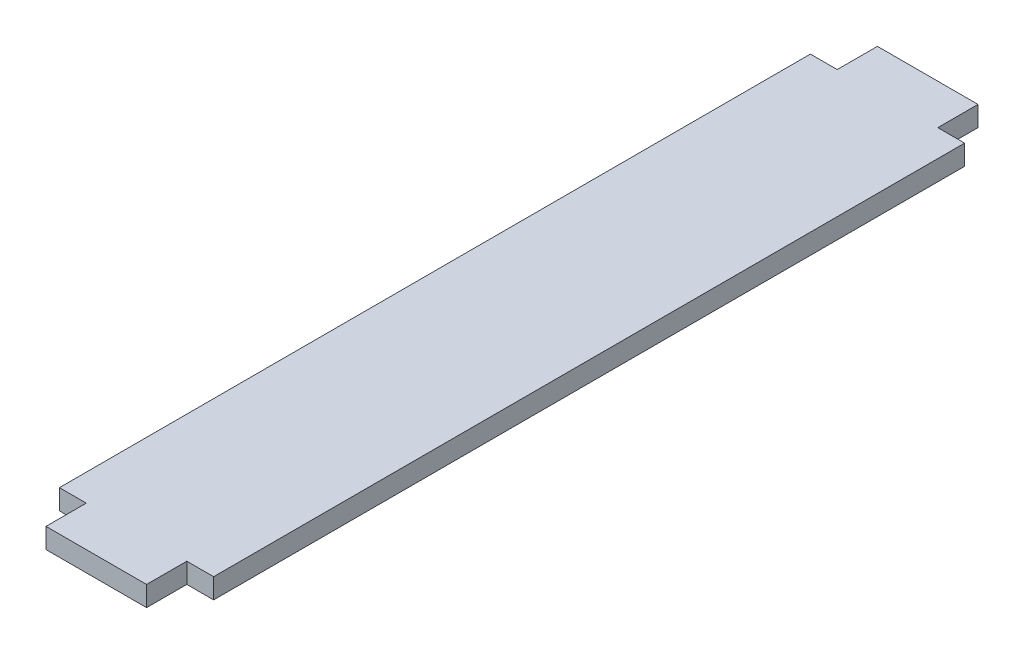
SolidWorks part; units mm, degrees
material "AISI 304"
ref_plane "Front Plane" through (0, 0, 0) normal (0, 0, 1) x (1, 0, 0)
ref_plane "Top Plane" through (0, 0, 0) normal (0, 1, 0) x (1, 0, 0)
ref_plane "Right Plane" through (0, 0, 0) normal (1, 0, 0) x (0, 0, -1)
sketch "Sketch1" plane through (0, 0, 0) normal (0, 1, 0) x (1, 0, 0)
  line L0 (3.75, 28) -> (5.75, 28)
  line L1 (-5.75, -28) -> (-3.75, -28)
  line L2 (-5.75, -28) -> (-5.75, -18.6)
  line L3 (-5.75, 28) -> (-3.75, 28)
  line L4 (5.75, -28) -> (5.75, -13.6)
  line L5 (-5.75, -28) -> (5.75, 28) construction
  line L6 (-5.75, 28) -> (5.75, -28) construction
  line L8 (3.75, 28) -> (3.75, 31)
  line L9 (3.75, 31) -> (-3.75, 31)
  line L10 (-3.75, 28) -> (-3.75, 31)
  line L12 (-3.75, -28) -> (-3.75, -31)
  line L13 (-3.75, -31) -> (3.75, -31)
  line L14 (3.75, -28) -> (3.75, -31)
  line L15 (3.75, -28) -> (5.75, -28)
  line L16 (-5.75, -16.9) -> (-5.75, 28)
  line L21 (5.75, -11.9) -> (5.75, 28)
  line L26 (-5.75, -18.6) -> (-5.75, -16.9)
  line L27 (5.75, -13.6) -> (5.75, -11.9)
  point P0 (0, 0)
  dimension "D1" = 7.5
  dimension "D2" = 2
  dimension "D3" = 2
  dimension "D4" = 3
  dimension "D5" = 2
  dimension "D6" = 2
  dimension "D7" = 3
  dimension "D8" = 56
extrude "Boss-Extrude1" add sketch "Sketch1" along normal blind 1.5
